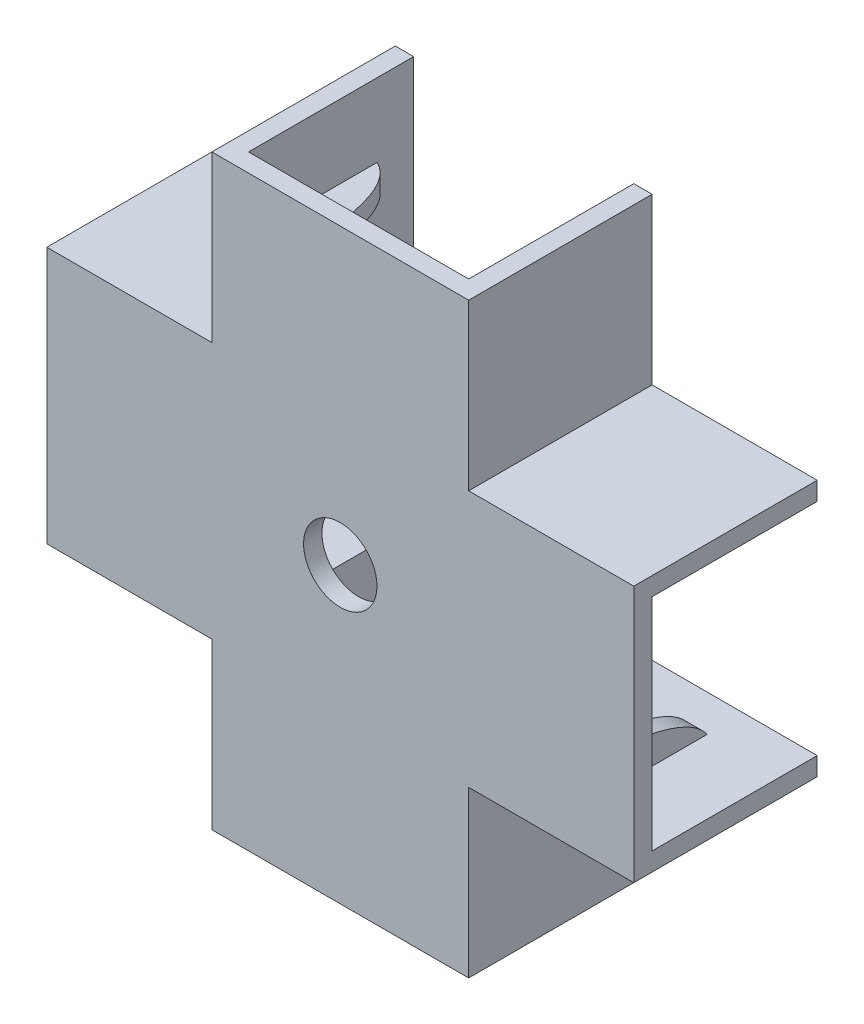
SolidWorks part; units mm, degrees
ref_plane "Alzado" through (0, 0, 0) normal (0, 0, 1) x (1, 0, 0)
ref_plane "Planta" through (0, 0, 0) normal (0, 1, 0) x (1, 0, 0)
ref_plane "Vista lateral" through (0, 0, 0) normal (1, 0, 0) x (0, 0, -1)
sketch "Croquis1" plane through (0, 0, 0) normal (0, 0, 1) x (1, 0, 0)
  line L0 (117743.4169, 152337.8366) -> (131743.4169, 152337.8366)
  line L1 (131743.4169, 152337.8366) -> (131743.4169, 161337.8366)
  line L2 (131743.4169, 161337.8366) -> (140743.4169, 161337.8366)
  line L3 (140743.4169, 161337.8366) -> (140743.4169, 175337.8366)
  line L4 (140743.4169, 175337.8366) -> (117743.4169, 175337.8366)
  line L5 (117743.4169, 175337.8366) -> (117743.4169, 152337.8366)
  line L6 (118743.4169, 152337.8366) -> (118743.4169, 166437.8366)
  line L7 (118743.4169, 174337.8366) -> (122843.4169, 174337.8366)
  line L8 (130743.4169, 152337.8366) -> (130743.4169, 162337.8366)
  line L9 (140743.4169, 162337.8366) -> (130743.4169, 162337.8366)
  line L10 (131743.4169, 161337.8366) -> (108743.4169, 161337.8366)
  line L11 (108743.4169, 161337.8366) -> (108743.4169, 162337.8366)
  line L12 (108743.4169, 162337.8366) -> (122843.4169, 162337.8366)
  line L13 (131743.4169, 161337.8366) -> (131743.4169, 184337.8366)
  line L14 (131743.4169, 184337.8366) -> (130743.4169, 184337.8366)
  line L15 (130743.4169, 184337.8366) -> (130743.4169, 170237.8366)
  line L16 (118743.4169, 174337.8366) -> (118743.4169, 184337.8366)
  line L17 (118743.4169, 184337.8366) -> (117743.4169, 184337.8366)
  line L18 (117743.4169, 184337.8366) -> (117743.4169, 175337.8366)
  line L19 (118743.4169, 174337.8366) -> (108743.4169, 174337.8366)
  line L20 (108743.4169, 174337.8366) -> (108743.4169, 175337.8366)
  line L21 (108743.4169, 175337.8366) -> (117743.4169, 175337.8366)
  line L22 (108743.4169, 174337.8366) -> (108743.4169, 162337.8366)
  line L23 (118743.4169, 184337.8366) -> (130743.4169, 184337.8366)
  line L24 (122743.4169, 174237.8366) -> (122743.4169, 172837.8366)
  line L25 (124243.4169, 171337.8366) -> (125243.4169, 171337.8366)
  line L26 (126743.4169, 172837.8366) -> (126743.4169, 174237.8366)
  line L27 (118843.4169, 170337.8366) -> (120243.4169, 170337.8366)
  line L28 (121743.4169, 168837.8366) -> (121743.4169, 167837.8366)
  line L29 (120243.4169, 166337.8366) -> (118843.4169, 166337.8366)
  line L30 (130643.4169, 170337.8366) -> (129243.4169, 170337.8366)
  line L31 (127743.4169, 168837.8366) -> (127743.4169, 167837.8366)
  line L32 (129243.4169, 166337.8366) -> (130643.4169, 166337.8366)
  line L33 (122743.4169, 162437.8366) -> (122743.4169, 163837.8366)
  line L34 (124243.4169, 165337.8366) -> (125243.4169, 165337.8366)
  line L35 (126743.4169, 163837.8366) -> (126743.4169, 162337.8366)
  line L36 (121743.4169, 168337.8366) -> (127743.4169, 168337.8366) construction
  line L37 (118743.4169, 170237.8366) -> (120243.4169, 170237.8366)
  line L38 (118843.4169, 174237.8366) -> (122743.4169, 174237.8366)
  line L39 (121643.4169, 168837.8366) -> (121643.4169, 167837.8366)
  line L40 (118843.4169, 162437.8366) -> (118843.4169, 166337.8366)
  line L41 (118843.4169, 162437.8366) -> (122743.4169, 162437.8366)
  line L42 (130643.4169, 174237.8366) -> (130643.4169, 170337.8366)
  line L43 (120243.4169, 166437.8366) -> (118743.4169, 166437.8366)
  line L44 (118743.4169, 174237.8366) -> (140743.4169, 174237.8366) construction
  line L45 (122843.4169, 162337.8366) -> (122843.4169, 163837.8366)
  line L46 (124243.4169, 165237.8366) -> (125243.4169, 165237.8366)
  line L47 (126643.4169, 163837.8366) -> (126643.4169, 162337.8366)
  line L48 (130743.4169, 170237.8366) -> (129243.4169, 170237.8366)
  line L49 (127843.4169, 168837.8366) -> (127843.4169, 167837.8366)
  line L50 (129243.4169, 166437.8366) -> (130743.4169, 166437.8366)
  line L51 (122843.4169, 174337.8366) -> (122843.4169, 172837.8366)
  line L52 (124243.4169, 171437.8366) -> (125243.4169, 171437.8366)
  line L53 (126643.4169, 172837.8366) -> (126643.4169, 174337.8366)
  line L54 (130643.4169, 166337.8366) -> (130643.4169, 162437.8366)
  line L55 (130743.4169, 166437.8366) -> (130743.4169, 162337.8366)
  line L56 (129243.4169, 166337.8366) -> (130743.4169, 166337.8366) construction
  line L57 (130743.4169, 170337.8366) -> (129243.4169, 170337.8366) construction
  line L58 (126643.4169, 174337.8366) -> (140743.4169, 174337.8366)
  line L59 (118743.4169, 174337.8366) -> (140743.4169, 174337.8366) construction
  line L60 (126743.4169, 174237.8366) -> (130643.4169, 174237.8366)
  line L61 (126743.4169, 172837.8366) -> (126743.4169, 174337.8366) construction
  line L62 (122743.4169, 174337.8366) -> (122743.4169, 172837.8366) construction
  line L63 (118743.4169, 170237.8366) -> (118743.4169, 174337.8366)
  line L64 (118843.4169, 170337.8366) -> (118843.4169, 174237.8366)
  line L65 (118743.4169, 170337.8366) -> (120243.4169, 170337.8366) construction
  line L66 (120243.4169, 166337.8366) -> (118743.4169, 166337.8366) construction
  line L67 (126743.4169, 162437.8366) -> (130643.4169, 162437.8366)
  line L68 (122743.4169, 162337.8366) -> (122743.4169, 163837.8366) construction
  line L69 (126643.4169, 162337.8366) -> (130743.4169, 162337.8366)
  arc A0 (125243.4169, 165337.8366) -> (126743.4169, 163837.8366) centre (125243.4169, 163837.8366) cw
  arc A1 (122743.4169, 163837.8366) -> (124243.4169, 165337.8366) centre (124243.4169, 163837.8366) cw
  arc A2 (127743.4169, 167837.8366) -> (129243.4169, 166337.8366) centre (129243.4169, 167837.8366) ccw
  arc A3 (129243.4169, 170337.8366) -> (127743.4169, 168837.8366) centre (129243.4169, 168837.8366) ccw
  arc A4 (125243.4169, 171337.8366) -> (126743.4169, 172837.8366) centre (125243.4169, 172837.8366) ccw
  arc A5 (122743.4169, 172837.8366) -> (124243.4169, 171337.8366) centre (124243.4169, 172837.8366) ccw
  arc A6 (120243.4169, 170337.8366) -> (121743.4169, 168837.8366) centre (120243.4169, 168837.8366) cw
  arc A7 (121743.4169, 167837.8366) -> (120243.4169, 166337.8366) centre (120243.4169, 167837.8366) cw
  circle A8 centre (124743.4169, 168337.8366) radius 2000
  arc A9 (120243.4169, 170237.8366) -> (121643.4169, 168837.8366) centre (120243.4169, 168837.8366) cw
  arc A10 (121643.4169, 167837.8366) -> (120243.4169, 166437.8366) centre (120243.4169, 167837.8366) cw
  arc A11 (122843.4169, 163837.8366) -> (124243.4169, 165237.8366) centre (124243.4169, 163837.8366) cw
  arc A12 (125243.4169, 165237.8366) -> (126643.4169, 163837.8366) centre (125243.4169, 163837.8366) cw
  arc A13 (129243.4169, 170237.8366) -> (127843.4169, 168837.8366) centre (129243.4169, 168837.8366) ccw
  arc A14 (127843.4169, 167837.8366) -> (129243.4169, 166437.8366) centre (129243.4169, 167837.8366) ccw
  arc A15 (122843.4169, 172837.8366) -> (124243.4169, 171437.8366) centre (124243.4169, 172837.8366) ccw
  arc A16 (125243.4169, 171437.8366) -> (126643.4169, 172837.8366) centre (125243.4169, 172837.8366) ccw
  circle A17 centre (124743.4169, 168337.8366) radius 1900
  point P34 (126743.4169, 163087.8366)
  point P39 (126743.4169, 165337.8366)
  point P42 (122743.4169, 165337.8366)
  point P45 (127743.4169, 166337.8366)
  point P48 (127743.4169, 170337.8366)
  point P51 (126743.4169, 171337.8366)
  point P54 (122743.4169, 171337.8366)
  point P57 (121743.4169, 170337.8366)
  point P60 (121743.4169, 166337.8366)
  point P105 (0, 0)
  dimension "D21" = 1500
  dimension "D22" = 4000
  dimension "D1" = 12000
  dimension "D2" = 1000
  dimension "D3" = 1000
  dimension "D4" = 1000
  dimension "D5" = 1000
  dimension "D6" = 12000
  dimension "D7" = 9000
  dimension "D8" = 9000
  dimension "D9" = 9000
  dimension "D10" = 9000
  dimension "D11" = 4000
  dimension "D12" = 4000
  dimension "D13" = 4000
  dimension "D14" = 4000
  dimension "D18" = 4000
  dimension "D19" = 4000
  dimension "D20" = 3000
  dimension "D23" = 100
  dimension "D24" = 100
  dimension "D25" = 100
  dimension "D26" = 100
ref_plane "Plano1" through (0, 161337.8366, 0) normal (0, 1, 0) x (1, 0, 0)
ref_plane "Plano2" through (0, 175337.8366, 0) normal (0, 1, 0) x (1, 0, 0)
ref_plane "Plano3" through (117743.4169, 0, 0) normal (1, 0, 0) x (0, 0, -1)
ref_plane "Plano4" through (131743.4169, 0, 0) normal (1, 0, 0) x (0, 0, -1)
ref_plane "Plano5" through (113243.4169, 0, 0) normal (1, 0, 0) x (0, 0, -1)
ref_plane "Plano6" through (0, 179837.8366, 0) normal (0, 1, 0) x (1, 0, 0)
ref_plane "Plano7" through (136243.4169, 0, 0) normal (1, 0, 0) x (0, 0, -1)
ref_plane "Plano8" through (0, 156837.8366, 0) normal (0, 1, 0) x (1, 0, 0)
sketch "Croquis2" plane through (0, 156837.8366, 0) normal (0, 1, 0) x (1, 0, 0)
  line L0 (117743.4169, 0) -> (131743.4169, 0) construction
  line L1 (117743.4169, 0) -> (131743.4169, 0)
  line L2 (131743.4169, 0) -> (131743.4169, 8000)
  line L3 (131743.4169, 8000) -> (130743.4169, 8000)
  line L4 (130743.4169, 8000) -> (130743.4169, 1000)
  line L5 (130743.4169, 1000) -> (118743.4169, 1000)
  line L6 (118743.4169, 1000) -> (118743.4169, 8000)
  line L7 (118743.4169, 8000) -> (117743.4169, 8000)
  line L8 (117743.4169, 8000) -> (117743.4169, 0)
  spline S0 degree 2 poles (130743.4169, 8000) (128761.6752, 7234.3483) (128743.4169, 1000) knots 0 0 0 0.590989 0.590989 0.590989
  spline S1 degree 2 poles (118743.4169, 8000) (120739.8111, 7120.5788) (120743.4169, 1000) knots 0 0 0 0.514461 0.514461 0.514461
  point P10 (0, 0)
  dimension "D1" = 1000
  dimension "D2" = 1000
  dimension "D3" = 1000
  dimension "D4" = 7000
  dimension "D5" = 7000
  dimension "D6" = 2000
  dimension "D7" = 2000
sketch "Croquis3" plane through (0, 179837.8366, 0) normal (0, 1, 0) x (1, 0, 0)
  line L0 (118743.4169, 1000) -> (118743.4169, 8000) construction
  line L1 (130743.4169, 1000) -> (118743.4169, 1000) construction
  line L2 (130743.4169, 8000) -> (130743.4169, 1000) construction
  line L3 (118743.4169, 1000) -> (118743.4169, 8000)
  line L4 (130743.4169, 1000) -> (118743.4169, 1000)
  line L5 (130743.4169, 8000) -> (130743.4169, 1000)
  parabola Q0 (118743.4169, 8000) -> (120743.4169, 1000) focus (118361.6774, 7241.9739) apex (118662.5082, 8033.1777) construction
  parabola Q1 (130743.4169, 8000) -> (128743.4169, 1000) focus (131040.6578, 7282.3326) apex (130778.3168, 8013.005) construction
  parabola Q2 (118743.4169, 8000) -> (120743.4169, 1000) focus (118361.6774, 7241.9739) apex (118662.5082, 8033.1777)
  parabola Q3 (130743.4169, 8000) -> (128743.4169, 1000) focus (131040.6578, 7282.3326) apex (130778.3168, 8013.005)
sketch "Croquis4" plane through (113243.4169, 0, 0) normal (1, 0, 0) x (0, 0, -1)
  line L0 (0, 174337.8366) -> (0, 162337.8366) construction
  line L1 (0, 174337.8366) -> (0, 162337.8366)
  line L2 (0, 162337.8366) -> (8000, 162337.8366)
  line L3 (0, 174337.8366) -> (8000, 174337.8366)
  spline S0 degree 2 poles (8000, 162337.8366) (6698.659, 164240.8241) (0, 164337.8366) knots 0 0 0 0.70753 0.70753 0.70753
  spline S1 degree 2 poles (8000, 174337.8366) (6599.8546, 172118.7435) (0, 172337.8366) knots 0 0 0 0.648378 0.648378 0.648378
  dimension "D1" = 8000
  dimension "D2" = 2000
  dimension "D3" = 2000
sketch "Croquis5" plane through (136243.4169, 0, 0) normal (1, 0, 0) x (0, 0, -1)
  line L0 (0, 162337.8366) -> (8000, 162337.8366) construction
  line L1 (0, 174337.8366) -> (0, 162337.8366) construction
  line L2 (0, 174337.8366) -> (8000, 174337.8366) construction
  line L3 (0, 162337.8366) -> (8000, 162337.8366)
  line L4 (0, 174337.8366) -> (0, 162337.8366)
  line L5 (0, 174337.8366) -> (8000, 174337.8366)
  parabola Q0 (8000, 162337.8366) -> (0, 164337.8366) focus (7402.6379, 161620.0634) apex (8222.0253, 161894.2353) construction
  parabola Q1 (8000, 174337.8366) -> (0, 172337.8366) focus (7073.338, 175098.4045) apex (8142.0414, 174597.2807) construction
  parabola Q2 (8000, 162337.8366) -> (0, 164337.8366) focus (7402.6379, 161620.0634) apex (8222.0253, 161894.2353)
  parabola Q3 (8000, 174337.8366) -> (0, 172337.8366) focus (7073.338, 175098.4045) apex (8142.0414, 174597.2807)
extrude "Saliente-Extruir1" add sketch "Croquis1" against normal blind 1000 contours L58 L13 L9 L3 | L13 L58 L3 L4 | L15 L58 L13 L4 | L14 L15 L4 L13 | L23 L16 L4 L15 | L17 L18 L4 L16 | L19 L16 L4 L5 | L21 L20 L19 L5 | L19 L22 L12 L5 | L12 L11 L10 L5 | L12 L5 L10 L6 | L6 L10 L5 L0 | L8 L10 L6 L0 | L1 L10 L8 L0 | L10 L13 L9 L8 | L13 L2 L3 L9 | A12 L46 A11 L45 L12 L6 L10 L8 L69 L47 | L49 A14 L50 L55 L9 L13 L58 L15 L48 A13 | L52 A16 L53 L58 L15 L4 L16 L7 L51 A15 | A10 L39 A9 L37 L63 L19 L5 L12 L6 L43 | L28 A7 L29 L40 L41 L33 A1 L34 A0 L35 L67 L54 L32 A2 L31 A3 L30 L42 L60 L26 A4 L25 A5 L24 L38 L64 L27 A6 A8 | A16 L52 A15 L51 L7 L63 L37 A9 L39 A10 L43 L6 L12 L45 A11 L46 A12 L47 L69 L35 A0 L34 A1 L33 L41 L40 L29 A7 L28 A6 L27 L64 L38 L24 A5 L25 A4 L26 L60 L42 L30 A3 L31 A2 L32 L54 L67 L55 region at (118243.4169, 156837.8366, 0) region at (124743.4169, 156837.8366, 0) region at (113243.4169, 161837.8366, 0) region at (118243.4169, 161837.8366, 0) region at (131243.4169, 156837.8366, 0) region at (124743.4169, 162689.636, 0) region at (113243.4169, 168337.8366, 0) region at (119095.2163, 168337.8366, 0) region at (131243.4169, 161837.8366, 0) region at (126910.2941, 163137.8366, 0) region at (118760.3875, 164387.8366, 0) region at (113243.4169, 174837.8366, 0) region at (118243.4169, 174837.8366, 0) region at (136243.4169, 161837.8366, 0) region at (130391.6175, 168337.8366, 0) region at (118243.4169, 179837.8366, 0) region at (124743.4169, 173986.0372, 0) region at (136243.4169, 168337.8366, 0) region at (124743.4169, 179837.8366, 0) region at (131243.4169, 174837.8366, 0) region at (136243.4169, 174837.8366, 0) region at (131243.4169, 179837.8366, 0)
extrude "Saliente-Extruir2" add sketch "Croquis1<6>" against normal blind 10000 contours L13 L58 L3 L4 | L15 L58 L13 L4 | L14 L15 L4 L13 | L17 L18 L4 L16 | L19 L16 L4 L5 | L21 L20 L19 L5 | L12 L11 L10 L5 | L12 L5 L10 L6 | L6 L10 L5 L0 | L1 L10 L8 L0 | L10 L13 L9 L8 | L13 L2 L3 L9 region at (118243.4169, 156837.8366, 0) region at (113243.4169, 161837.8366, 0) region at (118243.4169, 161837.8366, 0) region at (131243.4169, 156837.8366, 0) region at (131243.4169, 161837.8366, 0) region at (113243.4169, 174837.8366, 0) region at (118243.4169, 174837.8366, 0) region at (136243.4169, 161837.8366, 0) region at (118243.4169, 179837.8366, 0) region at (131243.4169, 174837.8366, 0) region at (136243.4169, 174837.8366, 0) region at (131243.4169, 179837.8366, 0)
sketch "Croquis1<6>" plane through (0, 0, 0) normal (0, 0, 1) x (1, 0, 0) same geometry as "Croquis1"
extrude "Saliente-Extruir3" add sketch "Croquis2" along normal blind 500 and the other way blind 500 contours L4 S0 L5 | S1 L6 L5 region at (119605.9639, 156837.8366, -3955.1574) region at (129880.6924, 156837.8366, -3967.5864)
extrude "Saliente-Extruir4" add sketch "Croquis3" along normal blind 500 and the other way blind 500 contours Q2 L3 L4 | L5 Q3 L4 region at (129880.6924, 179837.8366, -3967.5864) region at (119605.9639, 179837.8366, -3955.1574)
extrude "Saliente-Extruir5" add sketch "Croquis4" along normal blind 500 and the other way blind 500 contours L2 S0 L1 | S1 L3 L1 region at (113243.4169, 173449.622, -3378.0839) region at (113243.4169, 163181.6256, -3312.204)
extrude "Saliente-Extruir6" add sketch "Croquis5" along normal blind 500 and the other way blind 500 contours L3 Q2 L4 | Q3 L5 L4 region at (136243.4169, 163181.6256, -3312.204) region at (136243.4169, 173449.622, -3378.0839)
